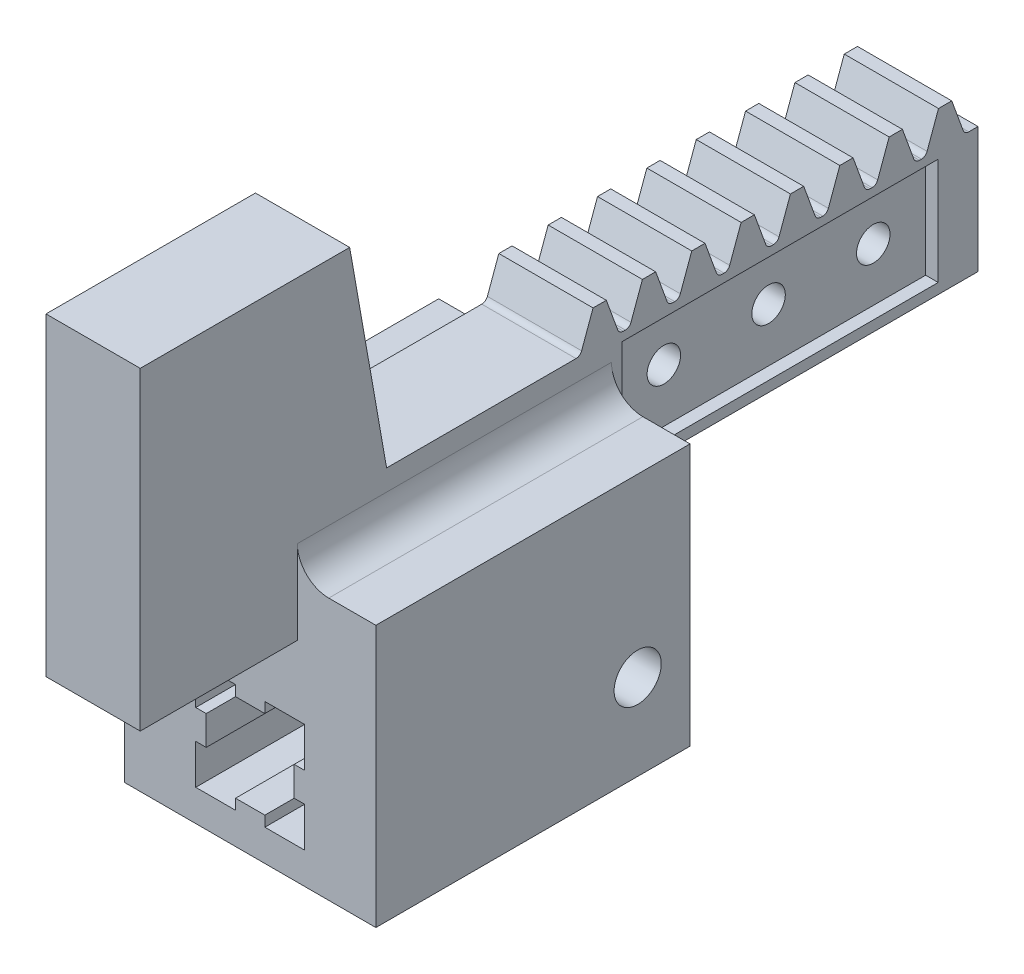
SolidWorks part; units mm, degrees
ref_plane "Front Plane" through (0, 0, 0) normal (0, 0, 1) x (1, 0, 0)
ref_plane "Top Plane" through (0, 0, 0) normal (0, 1, 0) x (1, 0, 0)
ref_plane "Right Plane" through (0, 0, 0) normal (1, 0, 0) x (0, 0, -1)
sketch "Esquisse1" plane through (0, 0, 0) normal (0, 0, 1) x (1, 0, 0)
  line L1 (-12, 12.5) -> (12, 12.5)
  line L2 (-12, 12.5) -> (-12, -12.5)
  line L3 (-12, -12.5) -> (12, -12.5)
  line L4 (12, 12.5) -> (12, -12.5)
  point P4 (0, -12.5)
  point P5 (-12, 0)
  dimension "D1" = 24
  dimension "D2" = 25
extrude "Main Extrusion" add sketch "Esquisse1" along normal blind 30
sketch "Esquisse3" plane through (0, 0, 0) normal (0, 0, -1) x (-1, 0, 0)
  line L0 (-5.2, 0.9) -> (-5.2, -2.9)
  line L1 (-5.2, -2.9) -> (-4.2, -2.9)
  line L2 (-4.2, -2.9) -> (-4.2, -5.7)
  line L3 (-4.2, -5.7) -> (-5.2, -5.7)
  line L4 (-5.2, -5.7) -> (-5.2, -9.5)
  line L5 (-5.2, -9.5) -> (-1.4, -9.5)
  line L6 (-1.4, -9.5) -> (-1.4, -8.5)
  line L7 (-1.4, -8.5) -> (1.4, -8.5)
  line L8 (1.4, -8.5) -> (1.4, -9.5)
  line L9 (1.4, -9.5) -> (5.2, -9.5)
  line L10 (5.2, -9.5) -> (5.2, -5.7)
  line L11 (5.2, -5.7) -> (4.2, -5.7)
  line L12 (4.2, -5.7) -> (4.2, -2.9)
  line L13 (4.2, -2.9) -> (5.2, -2.9)
  line L14 (5.2, -2.9) -> (5.2, 0.9)
  line L15 (5.2, 0.9) -> (1.4, 0.9)
  line L16 (1.4, 0.9) -> (1.4, -0.1)
  line L17 (1.4, -0.1) -> (-1.4, -0.1)
  line L18 (-1.4, -0.1) -> (-1.4, 0.9)
  line L19 (-1.4, 0.9) -> (-5.2, 0.9)
  line L21 (12, -12.5) -> (-12, -12.5) construction
  point P20 (0, -8.5)
  point P24 (0, -12.5)
  dimension "D1" = 2.8
  dimension "D2" = 10.4
  dimension "D3" = 1
  dimension "D4" = 1
  dimension "D5" = 3
extrude "Main Riding Hole" cut sketch "Esquisse3" against normal through all
sketch "Esquisse4" plane through (-12, 0, 0) normal (-1, 0, 0) x (0, 0, 1)
  line L1 (0, -5.7) -> (0, -2.9) construction
  line L2 (0, 12.5) -> (0, -12.5) construction
  circle A0 centre (5, -4.3) radius 2.25
  point P5 (0, -4.3)
  dimension "D1" = 4.5
  dimension "D2" = 5
extrude "TractorHole" cut sketch "Esquisse4" against normal blind 8
mirror "TractorHoleSymetry" about plane through (0, 0, 0) normal (1, 0, 0) of "TractorHole"
sketch "Esquisse5" plane through (0, 0, 0) normal (1, 0, 0) x (0, 0, -1)
  line L0 (-45, 7.5) -> (-45, 37.5)
  line L1 (-30, 12.5) -> (0, 12.5) construction
  line L2 (-45, 37.5) -> (-25, 37.5)
  line L3 (-25, 37.5) -> (-21.4735, 17.5)
  line L4 (-45, 7.5) -> (0, 7.5)
  line L5 (-21.4735, 17.5) -> (35, 17.5)
  line L6 (-30, -12.5) -> (-30, 12.5) construction
  line L7 (35, 17.5) -> (35, 5.5)
  line L9 (0, 7.5) -> (0, 5.5)
  line L10 (0, -12.5) -> (0, 12.5) construction
  line L11 (0, 5.5) -> (35, 5.5)
  line L12 (-30, -12.5) -> (0, -12.5) construction
  point P2 (0, 0)
  point P13 (0, 7.674)
  dimension "D1" = 30
  dimension "D2" = 20
  dimension "D3" = 18
  dimension "D4" = 15
  dimension "D5" = 12
  dimension "D6" = 100
  dimension "D7" = 35
  dimension "D8" = 5
extrude "ImpactPiece" add sketch "Esquisse5" against normal mid plane 9
fillet "Congé1" radius 3 2 edges at (-4.5, 12.5, 15) (4.5, 12.5, 15)
sketch "Esquisse8" plane through (0, 0, 0) normal (1, 0, 0) x (0, 0, -1)
  line L0 (30, 17.5) -> (31.2284, 20.875)
  line L1 (31.2284, 20.875) -> (32.4927, 20.875)
  line L2 (32.4927, 20.875) -> (33.7211, 17.5)
  line L3 (30, 17.5) -> (29.0087, 17.5) construction
  line L4 (30, 17.5) -> (33.7211, 17.5)
  line L5 (30.1365, 17.875) -> (28.8722, 17.875) construction
  line L6 (30, 17.5) -> (30, 1.1813) construction
  line L7 (29.0087, 17.5) -> (28.3262, 19.375) construction
  line L8 (28.3262, 19.375) -> (33.0386, 19.375) construction
  line L9 (35, 17.5) -> (-21.4735, 17.5) construction
  line L10 (35, 5.5) -> (35, 17.5) construction
  point P6 (3.404, 3.2652)
  point P11 (0, 0)
  point P12 (-0.6321, -1.2869)
  point P13 (0, 0)
  point P14 (-1.3026, 0.5261)
  point P15 (0, 0)
  point P16 (37.3258, 19.2704)
  point P17 (42.9099, 20)
  dimension "D1" = 20
  dimension "D2" = 1.5
  dimension "D3" = 3.375
  dimension "D4" = 4.7124
  dimension "D5" = 3
  dimension "D6" = 5
extrude "Boss.-Extru.1" add sketch "Esquisse8" along normal mid plane 9
fillet "Congé3" radius 0.57 2 edges at (0, 17.5, -30) (0, 17.5, -33.7211)
pattern_linear "Répétition linéaire1" count 8 spacing 4.7124 along (0, 0, 1) of "Boss.-Extru.1", "Congé3"
sketch "Esquisse9" plane through (4.5, 0, 0) normal (1, 0, 0) x (0, 0, -1)
  line L1 (1, 16.7) -> (31.2, 16.7)
  line L2 (1, 16.7) -> (1, 6.5)
  line L3 (1, 6.5) -> (31.2, 6.5)
  line L4 (31.2, 16.7) -> (31.2, 6.5)
  line L6 (0, 15.5) -> (0, 5.5) construction
  line L7 (0, 5.5) -> (35, 5.5) construction
  point P4 (0.817, 8.7896)
  dimension "D1" = 10.2
  dimension "D2" = 30.2
  dimension "D3" = 1
  dimension "D4" = 1
extrude "Enlèv. mat.-Extru.1" cut sketch "Esquisse9" against normal blind 1.2
sketch "Esquisse10" plane through (3.3, 0, 0) normal (1, 0, 0) x (0, 0, -1)
  line L0 (31.2, 6.5) -> (31.2, 16.7) construction
  line L1 (31.2, 6.5) -> (31.2, 16.7) construction
  circle A0 centre (26.2, 11.6) radius 1.6
  point P4 (0, 0)
  point P7 (31.2, 11.6)
  dimension "D1" = 3.2
  dimension "D2" = 5
extrude "Enlèv. mat.-Extru.2" cut sketch "Esquisse10" against normal through all
pattern_linear "Répétition linéaire2" count 3 spacing 10 along (0, 0, 1) of "Enlèv. mat.-Extru.2"
mirror "Symétrie1" about plane through (0, 0, 0) normal (1, 0, 0) of "Enlèv. mat.-Extru.1"
sketch "Esquisse11" plane through (0, 0, 0) normal (0, 0, -1) x (-1, 0, 0)
  line L0 (12, 12.5) -> (12, -12.5) construction
  line L1 (12, 1.9) -> (4.5, 1.9)
  line L2 (12, 1.9) -> (12, 6.9)
  line L3 (12, 6.9) -> (4.5, 6.9)
  line L4 (4.5, 1.9) -> (4.5, 6.9)
  line L5 (4.5, 15.5) -> (4.5, 5.5) construction
  line L6 (5.2, 0.9) -> (1.4, 0.9) construction
  dimension "D1" = 1
  dimension "D2" = 5
extrude "Enlèv. mat.-Extru.3" cut sketch "Esquisse11" against normal blind 20
